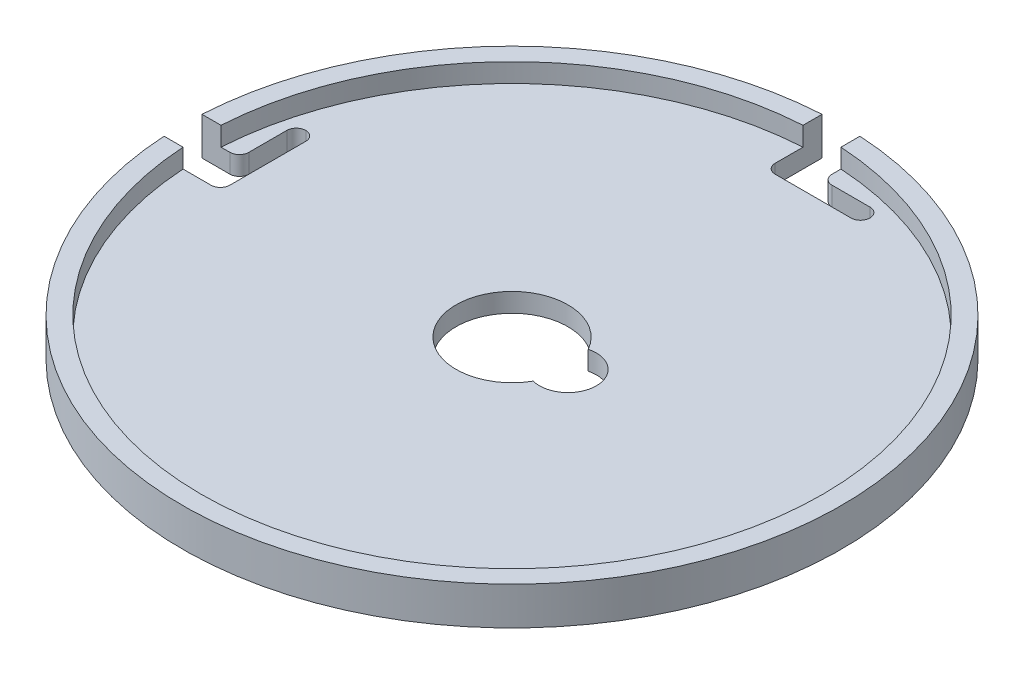
SolidWorks part; units mm, degrees
ref_plane "Front Plane" through (0, 0, 0) normal (0, 0, 1) x (1, 0, 0)
ref_plane "Top Plane" through (0, 0, 0) normal (0, 1, 0) x (1, 0, 0)
ref_plane "Right Plane" through (0, 0, 0) normal (1, 0, 0) x (0, 0, -1)
sketch "Sketch1" plane through (0, 0, 0) normal (0, 1, 0) x (1, 0, 0)
  circle A0 centre (0, 0) radius 32.75
  dimension "D1" = 65.5
extrude "Outer DIsk" add sketch "Sketch1" along normal blind 2
shell "Enclosement" thickness 2 removed face at (0, 2, 32.75) outward yes
sketch "Sketch2" plane through (0, 0, 0) normal (0, 1, 0) x (1, 0, 0)
  line L0 (-2, 34.75) -> (-2, 28.75)
  line L9 (-2, 34.75) -> (2, 34.75)
  line L10 (2, 34.75) -> (2, 30.75)
  line L11 (-2, 28.75) -> (8, 28.75)
  line L12 (2, 30.75) -> (8, 30.75)
  line L13 (8, 28.75) -> (8, 30.75)
  line L14 (2, 30.75) -> (2, 28.75)
  circle A1 centre (0, 0) radius 34.75 construction
  circle A3 centre (0, 0) radius 28.75 construction
  point P2 (0, 34.75)
  dimension "D1" = 4
  dimension "D2" = 6
  dimension "D3" = 2
  dimension "D4" = 10
extrude "Hook Release" cut sketch "Sketch2" against normal through all both and the other way through all contours L10 L9 L0 L11 L13 L12
sketch "Sketch3" plane through (0, 0, 0) normal (0, 1, 0) x (1, 0, 0)
  circle A0 centre (0, 0) radius 28.75 construction
  circle A1 centre (0, 0) radius 5.9
  circle A2 centre (5.9, 0) radius 3
  point P6 (0, 0)
  point P7 (0, 0)
  point P8 (0, 0)
  point P9 (0, 0)
  dimension "D1" = 11.8
  dimension "D3" = 6
  dimension "D2" = 5.9
pattern_circular "CirPattern1" count 2 over 90 about axis through (0, 2, 0) along (0, 1, 0) of "Hook Release"
extrude "Servo Motor Cutout" cut sketch "Sketch3" against normal through all both and the other way through all contours A2 A1 | A1 A2 | A1 A2 region at (4.4996, 0, 0) region at (7.026, 0, 0) region at (-0.586, 0, 0)
fillet "Fillet1" radius 1 8 edges at (-28.75, -1, 2) (-28.75, -1, -8) (-30.75, -1, -8) (-30.75, -1, -2) (8, -1, -28.75) (-2, -1, -28.75) (8, -1, -30.75) (2, -1, -30.75)
